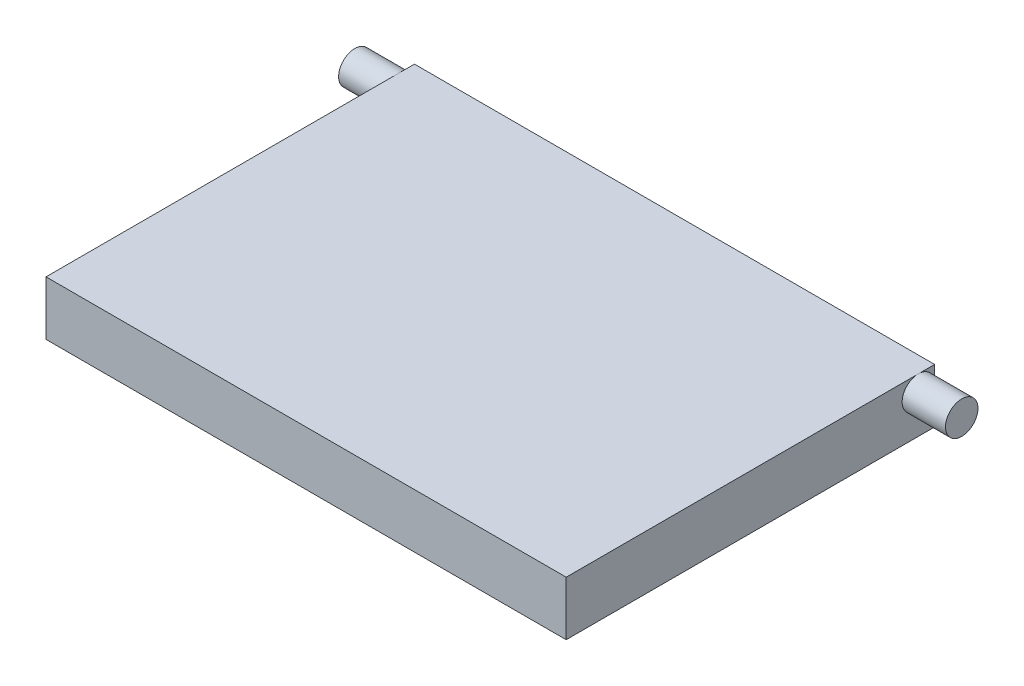
SolidWorks part; units mm, degrees
ref_plane "Front Plane" through (0, 0, 0) normal (0, 0, 1) x (1, 0, 0)
ref_plane "Top Plane" through (0, 0, 0) normal (0, 1, 0) x (1, 0, 0)
ref_plane "Right Plane" through (0, 0, 0) normal (1, 0, 0) x (0, 0, -1)
sketch "Sketch1" plane through (0, 0, 0) normal (0, 1, 0) x (1, 0, 0)
  line L1 (-12, -8.5) -> (12, -8.5)
  line L2 (-12, -8.5) -> (-12, 8.5)
  line L3 (-12, 8.5) -> (12, 8.5)
  line L4 (12, -8.5) -> (12, 8.5)
  line L5 (-12, -8.5) -> (12, 8.5) construction
  line L6 (-12, 8.5) -> (12, -8.5) construction
  point P0 (0, 0)
  dimension "D1" = 17
  dimension "D2" = 24
extrude "Boss-Extrude1" add sketch "Sketch1" along normal blind 2.5
sketch "Sketch2" plane through (0, 0, 0) normal (1, 0, 0) x (0, 0, -1)
  line L0 (-8.5, 2.5) -> (8.5, 2.5) construction
  line L4 (8.5, 2.5) -> (8.5, 0) construction
  circle A0 centre (7.75, 1.75) radius 0.75
  point P4 (0, 0)
  point P7 (0, 0)
  point P10 (0, 0)
  point P11 (0, 0)
  dimension "D1" = 1.5
extrude "Boss-Extrude2" add sketch "Sketch2" along normal mid plane 28
